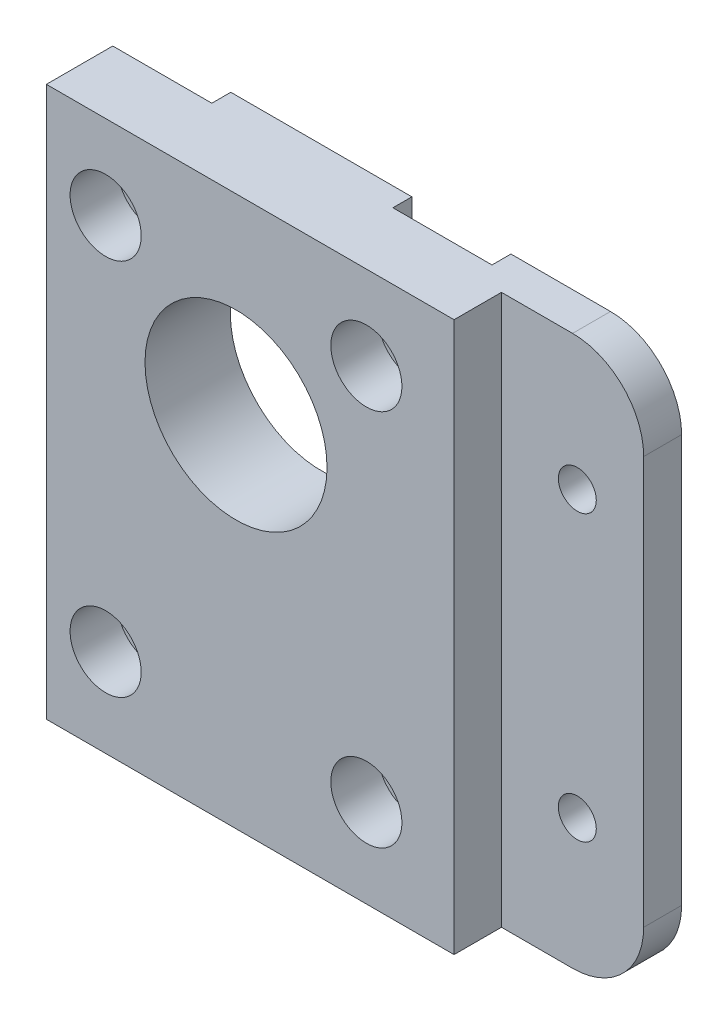
SolidWorks part; units mm, degrees
material "1060 Alloy"
ref_plane "Front Plane" through (0, 0, 0) normal (0, 0, 1) x (1, 0, 0)
ref_plane "Top Plane" through (0, 0, 0) normal (0, 1, 0) x (1, 0, 0)
ref_plane "Right Plane" through (0, 0, 0) normal (1, 0, 0) x (0, 0, -1)
sketch "Sketch1" plane through (0, 0, 0) normal (0, 0, 1) x (1, 0, 0)
  line L0 (-13.75, -19.7) -> (-9.6769, -16.8) construction
  line L3 (20, 29) -> (38, 29)
  line L8 (20, -29) -> (-20, -29)
  line L9 (20, -29) -> (20, 29) construction
  line L10 (38, 29) -> (38, -29)
  line L11 (20, 29) -> (-20, 29)
  line L14 (-20, -29) -> (-20, 29)
  line L15 (20, -29) -> (-20, 29) construction
  line L16 (20, 29) -> (-20, -29) construction
  line L17 (-16.186, -16.2786) -> (-12.1129, -13.3786)
  line L18 (-11.314, -23.1214) -> (-7.2409, -20.2214)
  line L19 (0, -29) -> (0, 29) construction
  line L22 (38, -29) -> (20, -29)
  line L23 (17.2075, -17.3155) -> (20, -21.3647)
  line L24 (9.55, -19.7) -> (9.55, -29)
  line L25 (-9.55, 20.15) -> (-9.55, 29)
  line L26 (-17.2075, 17.7655) -> (-20, 21.8147)
  line L27 (9.55, 20.15) -> (9.55, 29)
  line L28 (17.2075, 17.7655) -> (20, 21.8147)
  line L29 (20, 21.8147) -> (20, 29)
  line L30 (-16.186, -16.2786) -> (-20, -16.2786)
  line L31 (20, -29) -> (20, -21.3647)
  line L32 (-11.314, -29) -> (-11.314, -23.1214)
  circle A18 centre (-13.75, 20.15) radius 4.2
  circle A19 centre (13.75, 20.15) radius 4.2
  circle A20 centre (13.75, -19.7) radius 4.2
  arc A21 (-16.186, -16.2786) -> (-11.314, -23.1214) centre (-13.75, -19.7) ccw
  arc A22 (-7.2409, -20.2214) -> (-12.1129, -13.3786) centre (-9.6769, -16.8) ccw
  circle A23 centre (0, 8.8) radius 9.6
  circle A24 centre (-5.725, -6.1) radius 4.2
  circle A25 centre (5.725, -6.1) radius 4.2
  point P0 (0, 0)
  point P14 (-6.2555, -14.364)
  point P31 (-11.7135, -18.25)
  point P37 (5.725, -10.3)
  point P43 (20, 29)
  point P46 (-20, 29)
  dimension "D1" = 58
  dimension "D2" = 40
  dimension "D3" = 12.2
  dimension "D4" = 8.4
  dimension "D5" = 8.4
  dimension "D6" = 19.2
  dimension "D7" = 9.3
  dimension "D8" = 27.5
  dimension "D9" = 39.85
  dimension "D10" = 5
  dimension "D12" = 20.2
  dimension "D13" = 11.45
  dimension "D14" = 22.9
  dimension "D15" = 18
extrude "Boss-Extrude1" add sketch "Sketch1" along normal blind 2 contours L11 L14 L8 L9 A25 A24 A23 A22 L18 A21 L17 A20 A19 A18 region at (12.605, -0.4811, 0)
sketch "Sketch4" plane through (0, 0, 2) normal (0, 0, 1) x (1, 0, 0)
  line L0 (0, -29) -> (0, 29) construction
  line L6 (38, -29) -> (20, -29) construction
  line L8 (-20, -29) -> (38, -29)
  line L11 (38, -29) -> (38, 29)
  line L12 (-20, 29) -> (-20, -29)
  line L13 (-20, -16.2786) -> (-20, 21.8147) construction
  line L14 (-20, 29) -> (38, 29)
  line L15 (20, 29) -> (38, 29) construction
  line L16 (38, 29) -> (38, -29) construction
  circle A2 centre (13.75, -19.7) radius 2
  circle A3 centre (-13.75, 20.15) radius 2
  circle A4 centre (13.75, 20.15) radius 2
  circle A10 centre (-13.75, -19.7) radius 2
  circle A11 centre (0, 8.8) radius 9.6
  circle A12 centre (0, 8.8) radius 9.6 construction
  dimension "D1" = 4
extrude "Boss-Extrude3" add sketch "Sketch4" along normal blind 2
sketch "Sketch5" plane through (0, 0, 4) normal (0, 0, 1) x (1, 0, 0)
  line L0 (-20, 0) -> (38, 0) construction
  line L3 (-20, 29) -> (-20, -29) construction
  line L4 (38, -29) -> (38, 29) construction
  circle A0 centre (31, 15) radius 2
  circle A1 centre (31, -15) radius 2
  dimension "D1" = 4
  dimension "D2" = 15
  dimension "D3" = 51
extrude "Cut-Extrude1" cut sketch "Sketch5" against normal blind 4
ref_plane "Plane1" through (0, 0, 0) normal (0, 0, -1) x (-1, 0, 0)
sketch "Sketch6" plane through (0, 0, 4) normal (0, 0, 1) x (1, 0, 0)
  line L0 (23, 29) -> (23, -29)
  line L1 (38, 29) -> (-20, 29) construction
  line L2 (-20, -29) -> (38, -29) construction
  line L3 (38, -29) -> (38, 29) construction
  circle A52 centre (-13.75, 20.15) radius 3.75
  circle A53 centre (13.75, 20.15) radius 3.75
  circle A54 centre (31, 15) radius 2
  circle A55 centre (13.75, -19.7) radius 3.75
  circle A56 centre (-13.75, -19.7) radius 3.75
  circle A57 centre (31, -15) radius 2
  circle A59 centre (31, 15) radius 2 construction
  circle A60 centre (31, -15) radius 2 construction
  line M5 (-20, 29) -> (-20, -29)
  line M6 (-20, -29) -> (38, -29)
  line M7 (38, -29) -> (38, 29)
  line M8 (38, 29) -> (-20, 29)
  circle M11 centre (0, 8.8) radius 9.6
  dimension "D1" = 7.5
  dimension "D2" = 15
extrude "Boss-Extrude4" add sketch "Sketch6" along normal blind 5 contours A57 A56 A55 A54 A53 A52 M8 M5 M6 M7 M11 region at (1.8449, -1.2761, 4)
sketch "Sketch7" plane through (0, 0, 4) normal (0, 0, 1) x (1, 0, 0)
  line L0 (38, -29) -> (38, 29) construction
  line L1 (30.5, 29) -> (38, 29)
  line L2 (38, 29) -> (38, 21.5)
  line L3 (-20, 0) -> (38, 0) construction
  line L4 (-20, 29) -> (-20, -29) construction
  line L5 (38, -29) -> (38, -21.5)
  line L6 (30.5, -29) -> (38, -29)
  arc A0 (38, 21.5) -> (30.5, 29) centre (30.5, 21.5) ccw
  arc A1 (38, -21.5) -> (30.5, -29) centre (30.5, -21.5) cw
  dimension "D1" = 15
extrude "Cut-Extrude2" cut sketch "Sketch7" against normal through all
